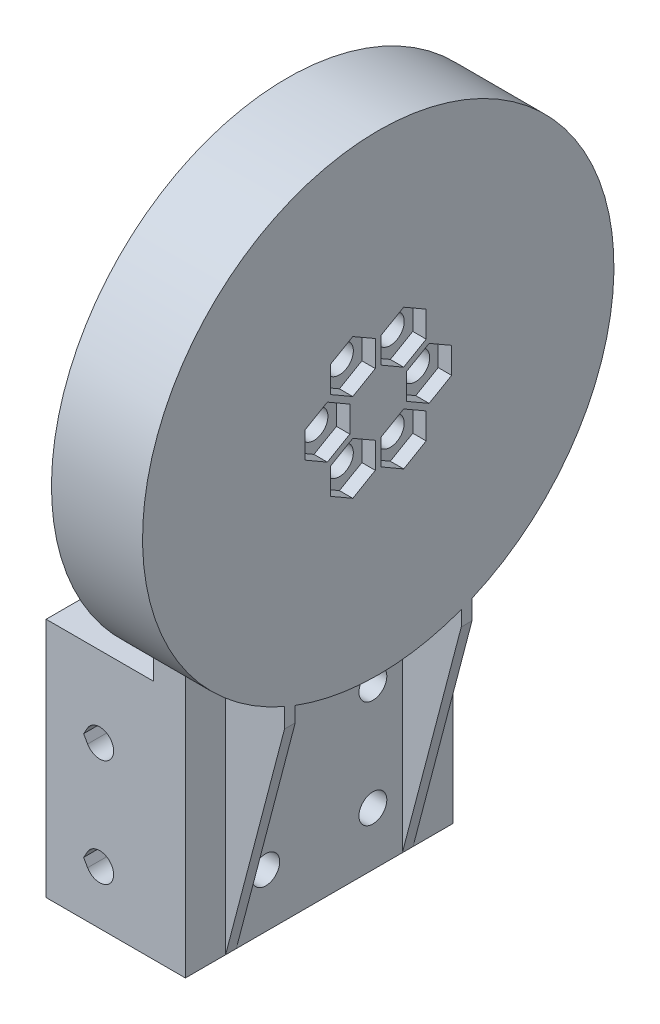
SolidWorks part; units mm, degrees
ref_plane "Front Plane" through (0, 0, 0) normal (0, 0, 1) x (1, 0, 0)
ref_plane "Top Plane" through (0, 0, 0) normal (0, 1, 0) x (1, 0, 0)
ref_plane "Right Plane" through (0, 0, 0) normal (1, 0, 0) x (0, 0, -1)
sketch "Sketch1" plane through (0, 0, 0) normal (1, 0, 0) x (0, 0, -1)
  line L0 (0, 0) -> (4.75, 8.2272) construction
  line L1 (0, -21.4441) -> (0, 21.4441) construction
  circle A0 centre (0, 0) radius 9.5 construction
  circle A7 centre (0, 0) radius 22.5
  circle A8 centre (0, 0) radius 30
  circle A9 centre (0, 0) radius 44
  circle A10 centre (4.75, 8.2272) radius 2.6
  circle A11 centre (9.5, 0) radius 2.6
  circle A12 centre (4.75, -8.2272) radius 2.6
  circle A13 centre (-4.75, -8.2272) radius 2.6
  circle A14 centre (-9.5, 0) radius 2.6
  circle A15 centre (-4.75, 8.2272) radius 2.6
  point P18 (0, 0)
  point P22 (0, 0)
  dimension "D1" = 19
  dimension "D2" = 5.2
  dimension "D4" = 60
  dimension "D5" = 45
  dimension "D6" = 88
  dimension "D7" = 30
  dimension "D3" = 6
extrude "Boss-Extrude1" add sketch "Sketch1" along normal blind 5 contours A7 A11 A12 A13 A14 | A8 A7 | A9 A8 region at (0, 0, 0) region at (0, 0, 29.1515) region at (0, 0, 42.7555)
extrude "Boss-Extrude2" add sketch "Sketch1<3>" against normal blind 4.5 contours A9 | A7
sketch "Sketch1<3>" plane through (0, 0, 0) normal (1, 0, 0) x (0, 0, -1) same geometry as "Sketch1"
sketch "Sketch2" plane through (-4.5, 0, 0) normal (-1, 0, 0) x (0, 0, 1)
  circle A0 centre (0, 0) radius 37.7
  circle A1 centre (0, 0) radius 44
  dimension "D1" = 75.4
  dimension "D2" = 88
extrude "Boss-Extrude3" add sketch "Sketch2" along normal blind 7.5
sketch "Sketch3" plane through (-12, 0, 0) normal (-1, 0, 0) x (0, 0, 1)
  line L0 (0, 0) -> (0, -82.3798) construction
  line L1 (25, -44) -> (-25, -44) construction
  line L2 (-25, -86) -> (25, -86)
  line L3 (-25, -86) -> (-25, -36.2077)
  line L5 (25, -86) -> (25, -36.2077)
  circle A0 centre (0, 0) radius 44 construction
  circle A2 centre (0, 0) radius 44
  arc A3 (-25, -36.2077) -> (25, -36.2077) centre (0, 0) ccw
  point P12 (0, -44)
  dimension "D1" = 50
  dimension "D2" = 25
  dimension "D3" = 42
  dimension "D4" = 0
extrude "Boss-Extrude4" add sketch "Sketch3" against normal blind 6
sketch "Sketch4" plane through (-4.5, 0, 0) normal (-1, 0, 0) x (0, 0, 1)
  circle A0 centre (0, 0) radius 35.25
  dimension "D1" = 70.5
extrude "Cut-Extrude1" cut sketch "Sketch4" against normal blind 1
sketch "Sketch5" plane through (-12, 0, 0) normal (-1, 0, 0) x (0, 0, 1)
  line L0 (-25, -36.2077) -> (-25, -86) construction
  line L1 (-25, -46) -> (25, -46)
  line L2 (-25, -46) -> (-25, -41)
  line L3 (-25, -41) -> (25, -41)
  line L4 (25, -46) -> (25, -41)
  line L5 (25, -86) -> (25, -36.2077) construction
  line L6 (-25, -86) -> (25, -86) construction
  line L8 (-20.1, -46) -> (-25, -46)
  line L9 (-20.1, -46) -> (-20.1, -86)
  line L10 (-20.1, -86) -> (-25, -86)
  line L11 (-25, -46) -> (-25, -86)
  line L12 (20.1, -46) -> (25, -46)
  line L13 (20.1, -46) -> (20.1, -86)
  line L14 (20.1, -86) -> (25, -86)
  line L15 (25, -46) -> (25, -86)
  line M4 (-25, -36.2077) -> (-25, -86)
  line M5 (-25, -86) -> (25, -86)
  line M6 (25, -86) -> (25, -36.2077)
  dimension "D1" = 5
  dimension "D2" = 40
  dimension "D3" = 4.9
  dimension "D4" = 4.9
extrude "Boss-Extrude5" add sketch "Sketch5" along normal blind 20 contours L9 L1 M4 M5 | L3 L1 M4 M6 | L1 L13 M5 M6 region at (-12, -43.5, 0) region at (-12, -66, -22.55) region at (-12, -66, 22.55)
ref_plane "Plane1" through (0, 0, 16.5) normal (0, 0, 1) x (1, 0, 0)
ref_plane "Plane2" through (0, 0, -16.5) normal (0, 0, -1) x (-1, 0, 0)
sketch "Sketch6" plane through (0, 0, 16.5) normal (0, 0, 1) x (1, 0, 0)
  line L1 (5, -44) -> (5, 44) construction
  line L2 (5, -40) -> (-6, -40)
  line L3 (-6, -44) -> (-6, -36.2077) construction
  line L4 (-6, -40) -> (-6, -86)
  line L5 (5, -40) -> (5, -44)
  line L6 (5, -44) -> (-6, -86)
  dimension "D1" = 46
extrude "Boss-Extrude7" add sketch "Sketch6" along normal blind 1 and the other way blind 1
sketch "Sketch7" plane through (0, 0, -16.5) normal (0, 0, -1) x (-1, 0, 0)
  line L1 (-5, 44) -> (-5, -44) construction
  line L2 (-5, -40) -> (6, -40)
  line L3 (6, -36.2077) -> (6, -40.3702) construction
  line L4 (6, -40) -> (6, -86)
  line L5 (-5, -40) -> (-5, -44)
  line L6 (-5, -44) -> (6, -86)
  dimension "D1" = 46
extrude "Boss-Extrude8" add sketch "Sketch7" along normal blind 1 and the other way blind 1
sketch "Sketch8" plane through (-6, 0, 0) normal (1, 0, 0) x (0, 0, -1)
  line L0 (-10, -86) -> (-10, -34.0161) construction
  line L1 (15.5, -86) -> (-15.5, -86) construction
  line L2 (10, -86) -> (10, -33.8504) construction
  line L3 (-25, -86) -> (-25, -36.2077) construction
  line L4 (25, -36.2077) -> (25, -86) construction
  line L5 (-10, -56) -> (10, -56) construction
  line L6 (-10, -76) -> (10, -76) construction
  circle A0 centre (-10, -76) radius 2.6
  circle A1 centre (10, -76) radius 2.6
  circle A2 centre (-10, -56) radius 2.6
  circle A3 centre (10, -56) radius 2.6
  dimension "D5" = 5.2
  dimension "D6" = 5.2
  dimension "D7" = 5.2
  dimension "D8" = 5.2
  dimension "D1" = 15
  dimension "D2" = 15
  dimension "D3" = 10
  dimension "D4" = 20
extrude "Cut-Extrude2" cut sketch "Sketch8" against normal through all
sketch "Sketch9" plane through (0, 0, 25) normal (0, 0, 1) x (1, 0, 0)
  line L0 (-6, -86) -> (-32, -86) construction
  line L1 (-32, -86) -> (-32, -41) construction
  line L2 (-22, -76) -> (-22, -56) construction
  line L3 (-22, -56) -> (-32, -56) construction
  line L4 (-32, -41) -> (-32, -86) construction
  line L5 (-22, -76) -> (-32, -76) construction
  line L6 (-24.2533, -54.7029) -> (-25, -56)
  line L7 (-25, -56) -> (-24.2533, -57.2971)
  line L8 (-24.2533, -74.7029) -> (-25, -76)
  line L9 (-25, -76) -> (-24.2533, -77.2971)
  circle A0 centre (-22, -76) radius 2.6
  circle A1 centre (-22, -56) radius 2.6
  dimension "D3" = 5.2
  dimension "D4" = 5.2
  dimension "D1" = 10
  dimension "D2" = 20
  dimension "D5" = 10
  dimension "D6" = 3
  dimension "D7" = 3
extrude "Cut-Extrude3" cut sketch "Sketch9" against normal through all contours A1 | A1 L6 L7 | A0 | A0 L8 L9 region at (-24.6867, -56, 25) region at (-22, -56, 25) region at (-24.6867, -76, 25) region at (-22, -76, 25)
sketch "Sketch10" plane through (5, 0, 0) normal (1, 0, 0) x (0, 0, -1)
  line L0 (9.5, -4.8497) -> (13.7, -2.4249)
  line L1 (8.95, 5.8024) -> (8.95, 10.6521)
  line L2 (8.95, 10.6521) -> (4.75, 13.077)
  line L3 (4.75, 13.077) -> (0.55, 10.6521)
  line L4 (0.55, 10.6521) -> (0.55, 5.8024)
  line L5 (0.55, 5.8024) -> (4.75, 3.3775)
  line L6 (4.75, 3.3775) -> (8.95, 5.8024)
  line L7 (13.7, -2.4249) -> (13.7, 2.4249)
  line L8 (13.7, 2.4249) -> (9.5, 4.8497)
  line L9 (9.5, 4.8497) -> (5.3, 2.4249)
  line L10 (5.3, 2.4249) -> (5.3, -2.4249)
  line L11 (5.3, -2.4249) -> (9.5, -4.8497)
  line L12 (0.55, -10.6521) -> (4.75, -13.077)
  line L13 (4.75, -13.077) -> (8.95, -10.6521)
  line L14 (8.95, -10.6521) -> (8.95, -5.8024)
  line L15 (8.95, -5.8024) -> (4.75, -3.3775)
  line L16 (4.75, -3.3775) -> (0.55, -5.8024)
  line L17 (0.55, -5.8024) -> (0.55, -10.6521)
  line L18 (-8.95, -5.8024) -> (-8.95, -10.6521)
  line L19 (-8.95, -10.6521) -> (-4.75, -13.077)
  line L20 (-4.75, -13.077) -> (-0.55, -10.6521)
  line L21 (-0.55, -10.6521) -> (-0.55, -5.8024)
  line L22 (-0.55, -5.8024) -> (-4.75, -3.3775)
  line L23 (-4.75, -3.3775) -> (-8.95, -5.8024)
  line L24 (-9.5, 4.8497) -> (-13.7, 2.4249)
  line L25 (-13.7, 2.4249) -> (-13.7, -2.4249)
  line L26 (-13.7, -2.4249) -> (-9.5, -4.8497)
  line L27 (-9.5, -4.8497) -> (-5.3, -2.4249)
  line L28 (-5.3, -2.4249) -> (-5.3, 2.4249)
  line L29 (-5.3, 2.4249) -> (-9.5, 4.8497)
  line L30 (-0.55, 10.6521) -> (-4.75, 13.077)
  line L31 (-4.75, 13.077) -> (-8.95, 10.6521)
  line L32 (-8.95, 10.6521) -> (-8.95, 5.8024)
  line L33 (-8.95, 5.8024) -> (-4.75, 3.3775)
  line L34 (-4.75, 3.3775) -> (-0.55, 5.8024)
  line L35 (-0.55, 5.8024) -> (-0.55, 10.6521)
  line L36 (0, -17.4605) -> (0, 17.4605) construction
  line L37 (0, 0) -> (4.75, 8.2272) construction
  circle A0 centre (4.75, 8.2272) radius 4.2 construction
  point P10 (2.65, 4.5899)
  point P44 (0, 0)
  dimension "D4" = 9.5
  dimension "D3" = 30
  dimension "D1" = 8.4
  dimension "D2" = 6
extrude "Cut-Extrude4" cut sketch "Sketch10" against normal blind 2.5
sketch "Sketch11" plane through (5, 0, 0) normal (1, 0, 0) x (0, 0, -1)
  line L0 (-4.75, 8.2272) -> (-4.75, 11.277) construction
  line L1 (12.75, 1.8764) -> (9.5, 3.7528)
  line L2 (4.75, 11.98) -> (1.5, 10.1036)
  line L3 (1.5, 10.1036) -> (1.5, 6.3509)
  line L4 (1.5, 6.3509) -> (4.75, 4.4745)
  line L5 (4.75, 4.4745) -> (8, 6.3509)
  line L6 (8, 6.3509) -> (8, 10.1036)
  line L7 (8, 10.1036) -> (4.75, 11.98)
  line L8 (9.5, 3.7528) -> (6.25, 1.8764)
  line L9 (6.25, 1.8764) -> (6.25, -1.8764)
  line L10 (6.25, -1.8764) -> (9.5, -3.7528)
  line L11 (9.5, -3.7528) -> (12.75, -1.8764)
  line L12 (12.75, -1.8764) -> (12.75, 1.8764)
  line L13 (8, -10.1036) -> (8, -6.3509)
  line L14 (8, -6.3509) -> (4.75, -4.4745)
  line L15 (4.75, -4.4745) -> (1.5, -6.3509)
  line L16 (1.5, -6.3509) -> (1.5, -10.1036)
  line L17 (1.5, -10.1036) -> (4.75, -11.98)
  line L18 (4.75, -11.98) -> (8, -10.1036)
  line L19 (-4.75, -11.98) -> (-1.5, -10.1036)
  line L20 (-1.5, -10.1036) -> (-1.5, -6.3509)
  line L21 (-1.5, -6.3509) -> (-4.75, -4.4745)
  line L22 (-4.75, -4.4745) -> (-8, -6.3509)
  line L23 (-8, -6.3509) -> (-8, -10.1036)
  line L24 (-8, -10.1036) -> (-4.75, -11.98)
  line L25 (-12.75, -1.8764) -> (-9.5, -3.7528)
  line L26 (-9.5, -3.7528) -> (-6.25, -1.8764)
  line L27 (-6.25, -1.8764) -> (-6.25, 1.8764)
  line L28 (-6.25, 1.8764) -> (-9.5, 3.7528)
  line L29 (-9.5, 3.7528) -> (-12.75, 1.8764)
  line L30 (-12.75, 1.8764) -> (-12.75, -1.8764)
  line L31 (-8, 10.1036) -> (-8, 6.3509)
  line L32 (-8, 6.3509) -> (-4.75, 4.4745)
  line L33 (-4.75, 4.4745) -> (-1.5, 6.3509)
  line L34 (-1.5, 6.3509) -> (-1.5, 10.1036)
  line L35 (-1.5, 10.1036) -> (-4.75, 11.98)
  line L36 (-4.75, 11.98) -> (-8, 10.1036)
  circle A0 centre (-4.75, 8.2272) radius 2.4 construction
  arc A1 (-3.8941, 11.5553) -> (-5.6059, 11.5553) centre (-4.75, 11.277) ccw construction
  arc A7 (-1.5398, 9.2078) -> (-2.3957, 10.6902) centre (-2.2088, 9.8098) ccw construction
  arc A8 (-2.3957, 5.9952) -> (-1.5398, 7.4776) centre (-2.2088, 6.8756) ccw construction
  arc A9 (-5.6059, 5.1301) -> (-3.8941, 5.1301) centre (-4.75, 5.4084) ccw construction
  arc A10 (-7.9602, 7.4776) -> (-7.1043, 5.9952) centre (-7.2912, 6.8756) ccw construction
  arc A11 (-7.1043, 10.6902) -> (-7.9602, 9.2078) centre (-7.2912, 9.8098) ccw construction
  arc A12 (-3.8941, 11.5553) -> (-2.3957, 10.6902) centre (-2.6642, 11.9554) ccw construction
  arc A13 (-1.5398, 9.2078) -> (-1.5398, 7.4776) centre (-0.5785, 8.3427) ccw construction
  arc A14 (-2.3957, 5.9952) -> (-3.8941, 5.1301) centre (-2.6642, 4.7301) ccw construction
  arc A15 (-5.6059, 5.1301) -> (-7.1043, 5.9952) centre (-6.8358, 4.7301) ccw construction
  arc A16 (-7.9602, 7.4776) -> (-7.9602, 9.2078) centre (-8.9215, 8.3427) ccw construction
  arc A17 (-7.1043, 10.6902) -> (-5.6059, 11.5553) centre (-6.8358, 11.9554) ccw construction
  arc A18 (2.4957, 10.6325) -> (1.6398, 9.1501) centre (2.3088, 9.7521) ccw construction
  arc A19 (1.6398, 7.4199) -> (1.6398, 9.1501) centre (0.6785, 8.285) ccw construction
  arc A20 (1.6398, 7.4199) -> (2.4957, 5.9375) centre (2.3088, 6.8178) ccw construction
  arc A21 (3.9941, 5.0723) -> (2.4957, 5.9375) centre (2.7642, 4.6723) ccw construction
  arc A22 (3.9941, 5.0723) -> (5.7059, 5.0723) centre (4.85, 5.3507) ccw construction
  arc A23 (7.2043, 5.9375) -> (5.7059, 5.0723) centre (6.9358, 4.6723) ccw construction
  arc A24 (7.2043, 5.9375) -> (8.0602, 7.4199) centre (7.3912, 6.8178) ccw construction
  arc A25 (8.0602, 9.1501) -> (8.0602, 7.4199) centre (9.0215, 8.285) ccw construction
  arc A26 (8.0602, 9.1501) -> (7.2043, 10.6325) centre (7.3912, 9.7521) ccw construction
  arc A27 (5.7059, 11.4976) -> (7.2043, 10.6325) centre (6.9358, 11.8976) ccw construction
  arc A28 (5.7059, 11.4976) -> (3.9941, 11.4976) centre (4.85, 11.2192) ccw construction
  arc A29 (2.4957, 10.6325) -> (3.9941, 11.4976) centre (2.7642, 11.8976) ccw construction
  circle A30 centre (4.75, 8.2272) radius 2.4 construction
  arc A31 (10.4559, 3.1549) -> (8.7441, 3.1549) centre (9.6, 2.8765) ccw construction
  arc A32 (7.2457, 2.2898) -> (8.7441, 3.1549) centre (7.5142, 3.5549) ccw construction
  arc A33 (7.2457, 2.2898) -> (6.3898, 0.8074) centre (7.0588, 1.4094) ccw construction
  arc A34 (6.3898, -0.9228) -> (6.3898, 0.8074) centre (5.4285, -0.0577) ccw construction
  arc A35 (6.3898, -0.9228) -> (7.2457, -2.4053) centre (7.0588, -1.5249) ccw construction
  arc A36 (8.7441, -3.2704) -> (7.2457, -2.4053) centre (7.5142, -3.6704) ccw construction
  arc A37 (8.7441, -3.2704) -> (10.4559, -3.2704) centre (9.6, -2.992) ccw construction
  arc A38 (11.9543, -2.4053) -> (10.4559, -3.2704) centre (11.6858, -3.6704) ccw construction
  arc A39 (11.9543, -2.4053) -> (12.8102, -0.9228) centre (12.1412, -1.5249) ccw construction
  arc A40 (12.8102, 0.8074) -> (12.8102, -0.9228) centre (13.7715, -0.0577) ccw construction
  arc A41 (12.8102, 0.8074) -> (11.9543, 2.2898) centre (12.1412, 1.4094) ccw construction
  arc A42 (10.4559, 3.1549) -> (11.9543, 2.2898) centre (11.6858, 3.5549) ccw construction
  circle A43 centre (9.5, 0) radius 2.4 construction
  arc A44 (7.9602, -7.4776) -> (7.1043, -5.9952) centre (7.2912, -6.8756) ccw construction
  arc A45 (5.6059, -5.1301) -> (7.1043, -5.9952) centre (6.8358, -4.7301) ccw construction
  arc A46 (5.6059, -5.1301) -> (3.8941, -5.1301) centre (4.75, -5.4084) ccw construction
  arc A47 (2.3957, -5.9952) -> (3.8941, -5.1301) centre (2.6642, -4.7301) ccw construction
  arc A48 (2.3957, -5.9952) -> (1.5398, -7.4776) centre (2.2088, -6.8756) ccw construction
  arc A49 (1.5398, -9.2078) -> (1.5398, -7.4776) centre (0.5785, -8.3427) ccw construction
  arc A50 (1.5398, -9.2078) -> (2.3957, -10.6902) centre (2.2088, -9.8098) ccw construction
  arc A51 (3.8941, -11.5553) -> (2.3957, -10.6902) centre (2.6642, -11.9554) ccw construction
  arc A52 (3.8941, -11.5553) -> (5.6059, -11.5553) centre (4.75, -11.277) ccw construction
  arc A53 (7.1043, -10.6902) -> (5.6059, -11.5553) centre (6.8358, -11.9554) ccw construction
  arc A54 (7.1043, -10.6902) -> (7.9602, -9.2078) centre (7.2912, -9.8098) ccw construction
  arc A55 (7.9602, -7.4776) -> (7.9602, -9.2078) centre (8.9215, -8.3427) ccw construction
  circle A56 centre (4.75, -8.2272) radius 2.4 construction
  arc A57 (-2.4957, -10.6325) -> (-1.6398, -9.1501) centre (-2.3088, -9.7521) ccw construction
  arc A58 (-1.6398, -7.4199) -> (-1.6398, -9.1501) centre (-0.6785, -8.285) ccw construction
  arc A59 (-1.6398, -7.4199) -> (-2.4957, -5.9375) centre (-2.3088, -6.8178) ccw construction
  arc A60 (-3.9941, -5.0723) -> (-2.4957, -5.9375) centre (-2.7642, -4.6723) ccw construction
  arc A61 (-3.9941, -5.0723) -> (-5.7059, -5.0723) centre (-4.85, -5.3507) ccw construction
  arc A62 (-7.2043, -5.9375) -> (-5.7059, -5.0723) centre (-6.9358, -4.6723) ccw construction
  arc A63 (-7.2043, -5.9375) -> (-8.0602, -7.4199) centre (-7.3912, -6.8178) ccw construction
  arc A64 (-8.0602, -9.1501) -> (-8.0602, -7.4199) centre (-9.0215, -8.285) ccw construction
  arc A65 (-8.0602, -9.1501) -> (-7.2043, -10.6325) centre (-7.3912, -9.7521) ccw construction
  arc A66 (-5.7059, -11.4976) -> (-7.2043, -10.6325) centre (-6.9358, -11.8976) ccw construction
  arc A67 (-5.7059, -11.4976) -> (-3.9941, -11.4976) centre (-4.85, -11.2192) ccw construction
  arc A68 (-2.4957, -10.6325) -> (-3.9941, -11.4976) centre (-2.7642, -11.8976) ccw construction
  circle A69 centre (-4.75, -8.2272) radius 2.4 construction
  arc A70 (-10.4559, -3.1549) -> (-8.7441, -3.1549) centre (-9.6, -2.8765) ccw construction
  arc A71 (-7.2457, -2.2898) -> (-8.7441, -3.1549) centre (-7.5142, -3.5549) ccw construction
  arc A72 (-7.2457, -2.2898) -> (-6.3898, -0.8074) centre (-7.0588, -1.4094) ccw construction
  arc A73 (-6.3898, 0.9228) -> (-6.3898, -0.8074) centre (-5.4285, 0.0577) ccw construction
  arc A74 (-6.3898, 0.9228) -> (-7.2457, 2.4053) centre (-7.0588, 1.5249) ccw construction
  arc A75 (-8.7441, 3.2704) -> (-7.2457, 2.4053) centre (-7.5142, 3.6704) ccw construction
  arc A76 (-8.7441, 3.2704) -> (-10.4559, 3.2704) centre (-9.6, 2.992) ccw construction
  arc A77 (-11.9543, 2.4053) -> (-10.4559, 3.2704) centre (-11.6858, 3.6704) ccw construction
  arc A78 (-11.9543, 2.4053) -> (-12.8102, 0.9228) centre (-12.1412, 1.5249) ccw construction
  arc A79 (-12.8102, -0.8074) -> (-12.8102, 0.9228) centre (-13.7715, 0.0577) ccw construction
  arc A80 (-12.8102, -0.8074) -> (-11.9543, -2.2898) centre (-12.1412, -1.4094) ccw construction
  arc A81 (-10.4559, -3.1549) -> (-11.9543, -2.2898) centre (-11.6858, -3.5549) ccw construction
  circle A82 centre (-9.5, 0) radius 2.4 construction
  circle A83 centre (4.75, 8.2272) radius 3.25 construction
  dimension "D1" = 4.8
  dimension "D2" = 6
  dimension "D4" = 1.8
  dimension "D5" = 1.2933
  dimension "D3" = 1.8
  dimension "D8" = 6.5
  dimension "D6" = 6
  dimension "D7" = 6
  dimension "D9" = 6
extrude "Boss-Extrude9" [suppressed] add sketch "Sketch11" against normal blind 1.4 separate body
equation "\"D2@Sketch3\"=\"D1@Sketch3\"/2"
